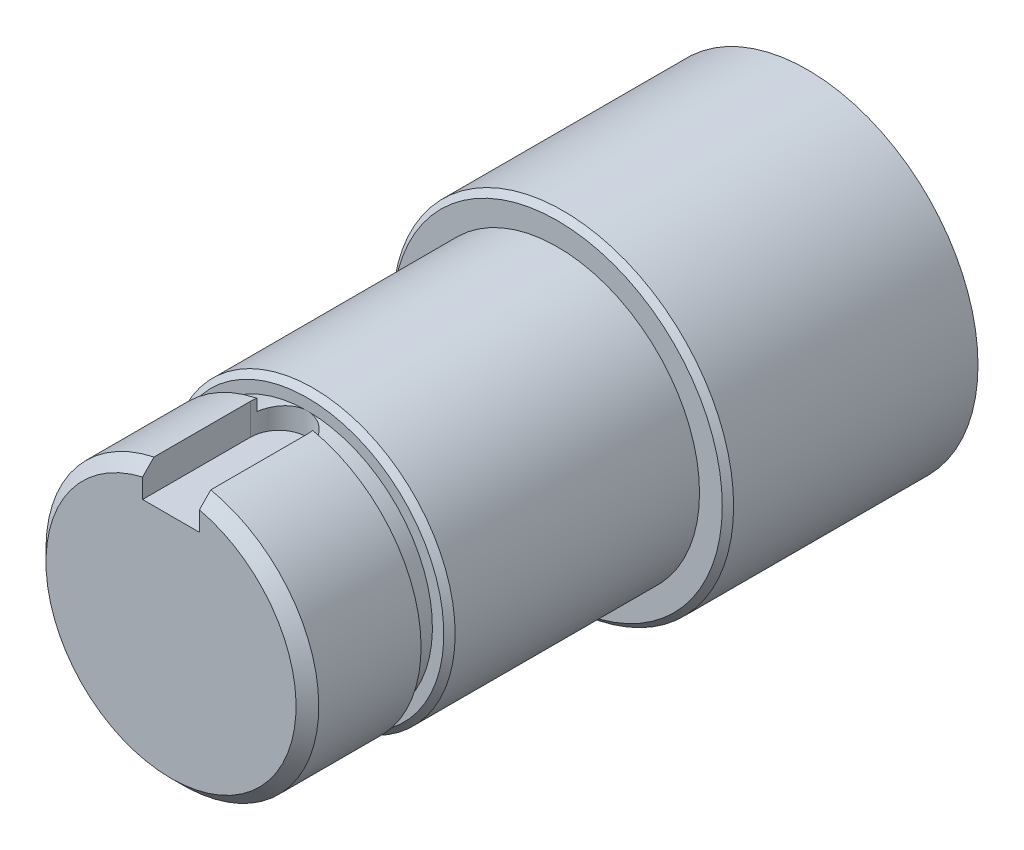
SolidWorks part; units mm, degrees
ref_plane "前视基准面" through (0, 0, 0) normal (0, 0, 1) x (1, 0, 0)
ref_plane "上视基准面" through (0, 0, 0) normal (0, 1, 0) x (1, 0, 0)
ref_plane "右视基准面" through (0, 0, 0) normal (1, 0, 0) x (0, 0, -1)
other "Configuration Table"
sketch "草图1" plane through (0, 0, 0) normal (1, 0, 0) x (0, 0, -1)
  line L0 (0, 0) -> (0, 12)
  line L1 (0, 12) -> (10, 12)
  line L2 (10, 12) -> (10, 11)
  line L3 (10, 11) -> (12, 11)
  line L4 (12, 11) -> (12, 12.5)
  line L5 (12, 12.5) -> (34, 12.5)
  line L6 (34, 12.5) -> (34, 15)
  line L7 (34, 15) -> (56, 15)
  line L8 (56, 15) -> (56, 0)
  line L9 (56, 0) -> (0, 0)
  line L10 (0, 0) -> (60.6914, 0) construction
  dimension "D1" = 30
  dimension "D2" = 25
  dimension "D3" = 24
  dimension "D4" = 12
  dimension "D5" = 44
  dimension "D6" = 22
  dimension "D7" = 22
  dimension "D8" = 2
revolve "旋转1" add sketch "草图1" angle 360 about L10
ref_plane "基准面1" through (0, 9, 0) normal (0, 1, 0) x (1, 0, 0)
sketch "草图2" plane through (0, 9, 0) normal (0, 1, 0) x (1, 0, 0)
  line L0 (-2.5, 9.5) -> (-2.5, 0)
  line L1 (-12, 0) -> (12, 0) construction
  line L2 (2.5, 9.5) -> (2.5, 0)
  line L3 (2.5, 0) -> (-2.5, 0)
  line L4 (-11, 12) -> (11, 12) construction
  arc A0 (2.5, 9.5) -> (-2.5, 9.5) centre (0, 9.5) ccw
  dimension "D1" = 5
extrude "切除-拉伸1" cut sketch "草图2" along normal through all
chamfer "倒角1" distance 1 angle 45 1 edges at (0, -12, 0)
chamfer "倒角2" distance 0.5 angle 45 2 edges at (12.5, 0, -12) (15, 0, -34)
